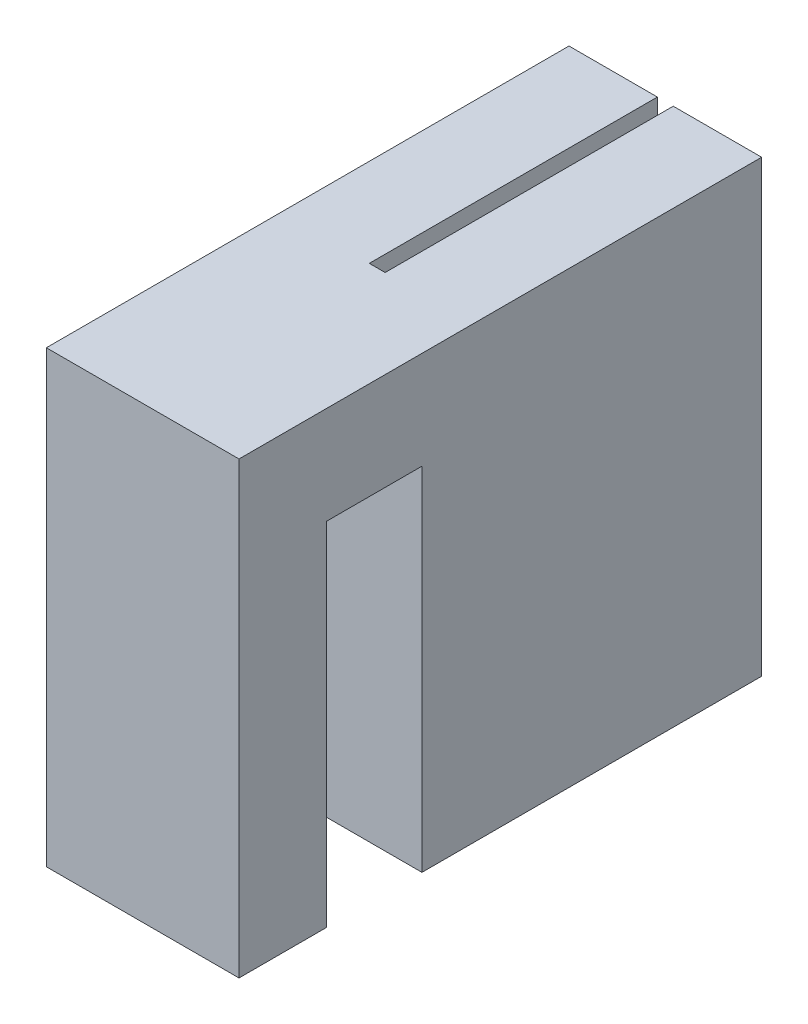
SolidWorks part; units mm, degrees
ref_plane "Front Plane" through (0, 0, 0) normal (0, 0, 1) x (1, 0, 0)
ref_plane "Top Plane" through (0, 0, 0) normal (0, 1, 0) x (1, 0, 0)
ref_plane "Right Plane" through (0, 0, 0) normal (1, 0, 0) x (0, 0, -1)
sketch "Sketch1" plane through (0, 0, 0) normal (1, 0, 0) x (0, 0, -1)
  line L0 (5.015, 0) -> (5.015, 20.2184)
  line L1 (0, 25.8349) -> (30.0377, 25.8349)
  line L2 (0, 25.8349) -> (0, 0)
  line L3 (0, 0) -> (30.0377, 0)
  line L4 (30.0377, 25.8349) -> (30.0377, 0)
  line L5 (5.015, 20.2184) -> (10.515, 20.2184)
  line L6 (10.515, 20.2184) -> (10.515, 0)
  line L7 (13.48, 25.8349) -> (13.48, 9.9337)
  line L8 (13.48, 9.9337) -> (30.0377, 9.9337)
  dimension "D1" = 5.5
extrude "Boss-Extrude1" add sketch "Sketch1" against normal blind 0.912 contours L8 L7 L1 L2 L3 L0 L5 L6 L4 region at (0, 10.4384, -12.6083)
extrude "Boss-Extrude2" add sketch "Sketch1<3>" along normal blind 5.08 contours L7 L8 L4 L1 | L8 L7 L1 L2 L3 L0 L5 L6 L4 region at (0, 10.4384, -12.6083) region at (0, 17.8843, -21.7588)
sketch "Sketch1<3>" plane through (0, 0, 0) normal (1, 0, 0) x (0, 0, -1) same geometry as "Sketch1"
sketch "Sketch2" plane through (-0.912, 0, 0) normal (-1, 0, 0) x (0, 0, 1)
  line L0 (-30.0377, 25.8349) -> (0, 25.8349)
  line L1 (0, 25.8349) -> (0, 0)
  line L2 (0, 0) -> (-5.015, 0)
  line L3 (-5.015, 0) -> (-5.015, 20.2184)
  line L4 (-5.015, 20.2184) -> (-10.515, 20.2184)
  line L5 (-10.515, 20.2184) -> (-10.515, 0)
  line L6 (-10.515, 0) -> (-30.0377, 0)
  line L7 (-30.0377, 0) -> (-30.0377, 25.8349)
extrude "Boss-Extrude3" add sketch "Sketch2" along normal blind 5.08
